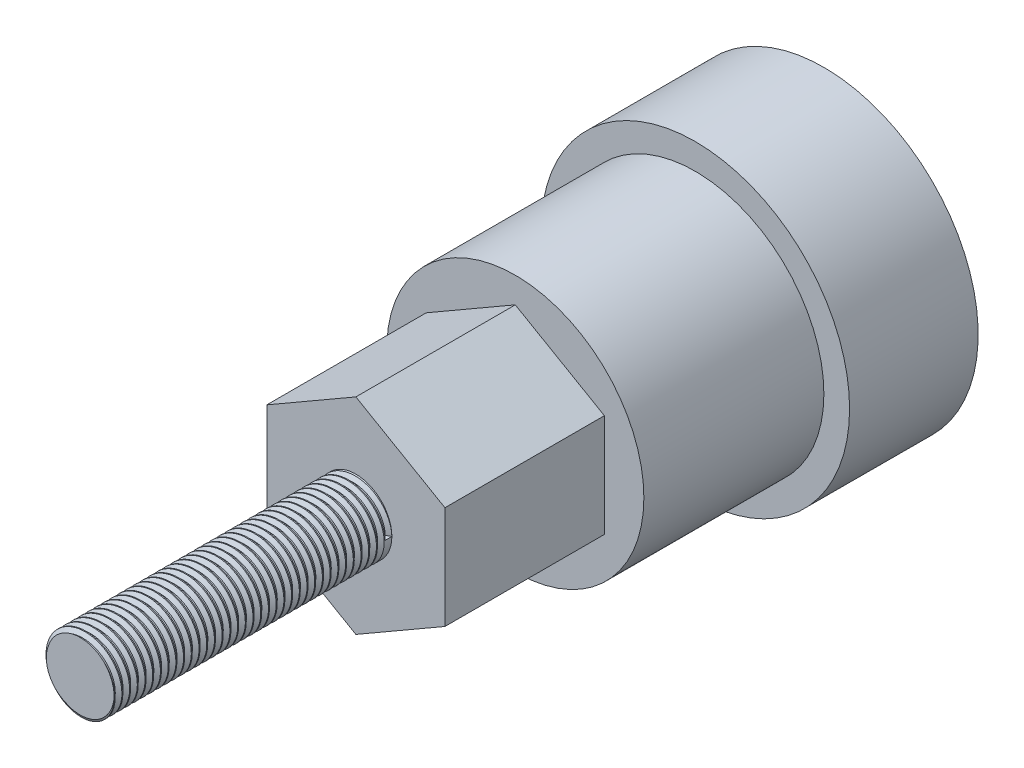
SolidWorks part; units mm, degrees
material "AISI 4340 Steel, annealed"
ref_plane "Front Plane" through (0, 0, 0) normal (0, 0, 1) x (1, 0, 0)
ref_plane "Top Plane" through (0, 0, 0) normal (0, 1, 0) x (1, 0, 0)
ref_plane "Right Plane" through (0, 0, 0) normal (1, 0, 0) x (0, 0, -1)
sketch "Sketch1" plane through (0, 0, 0) normal (0, 0, 1) x (1, 0, 0)
  circle A0 centre (0, 0) radius 30
  dimension "D1" = 60
extrude "Boss-Extrude1" add sketch "Sketch1" along normal blind 40
sketch "Sketch13" plane through (0, 0, 40) normal (0, 0, 1) x (1, 0, 0)
  circle A0 centre (0, 0) radius 25
  dimension "D1" = 50
extrude "Boss-Extrude7" add sketch "Sketch13" along normal blind 35
sketch "Sketch14" plane through (0, 0, 75) normal (0, 0, 1) x (1, 0, 0)
  line L5 (-19, 19) -> (19, -19) construction
  line L6 (-19, -19) -> (19, 19) construction
  line L7 (0, 20) -> (-17.3205, 10)
  line L8 (-17.3205, 10) -> (-17.3205, -10)
  line L9 (-17.3205, -10) -> (0, -20)
  line L10 (0, -20) -> (17.3205, -10)
  line L11 (17.3205, -10) -> (17.3205, 10)
  line L12 (17.3205, 10) -> (0, 20)
  circle A4 centre (0, 0) radius 17.3205 construction
  point P0 (0, 0)
  dimension "D1" = 38
extrude "Boss-Extrude8" add sketch "Sketch14" along normal blind 31
sketch "Sketch15" plane through (0, 0, 106) normal (0, 0, 1) x (1, 0, 0)
  circle A0 centre (0, 0) radius 7
  dimension "D1" = 14
extrude "Boss-Extrude9" add sketch "Sketch15" along normal blind 54
sketch "Sketch16" plane through (0, 0, 0) normal (0, 0, -1) x (-1, 0, 0)
  circle A0 centre (0, 0) radius 37.2164
extrude "Cut-Extrude2" cut sketch "Sketch16" against normal blind 15
hole_wizard "Ø2.5mm Dowel Hole2" [suppressed] positions "3DSketch3" profile "Sketch23" hole size "Ø2.5" standard "ANSI Metric"
sketch3d "3DSketch3"
  point P0 (-7, 0.0097, 120.8134)
sketch "Sketch23" plane through (-7, 0.0097, 120.8134) normal (0, 0, 1) x (-0.0014, -1, 0)
  line L0 (0, 0) -> (0, 37.0416)
  line L1 (0, 37.0416) -> (1.25, 37.0416)
  line L2 (1.25, 37.0416) -> (1.25, 0.025)
  line L3 (1.25, 0.025) -> (1.275, 0)
  line L5 (1.275, 0) -> (0, 0)
  line L6 (-1.25, 0.025) -> (-1.275, 0) construction
  line L11 (0, -6.35) -> (0, 107.95) construction
  dimension "Thru Hole Dia." = 2.5
  dimension "Thru Hole Depth" = 37.0416
  dimension "Near C'Sink Dia." = 2.55
  dimension "Near C'Sink Angle" = 90
thread "Thread1" pitch 1.5 method cut profile "Thread Profile1" start angle 0, offset 0, length 0, pitch 1.5, diameter 14
ref_plane "Plane1" through (7, 0, 106) normal (0, -1, 0) x (1, 0, 0)
sketch "Thread Profile1" plane through (7, 0, 106) normal (0, -1, 0) x (1, 0, 0)
  line L0 (0, 0) -> (0, 1.5) construction
  line L11 (0, 0) -> (0, 1.3125)
  line L12 (0, 1.3125) -> (-0.8119, 0.8437)
  line L13 (-0.8119, 0.8437) -> (-0.8119, 0.4687)
  line L15 (-0.8119, 0.4687) -> (0, 0)
  line L17 (-0.8119, 0.6562) -> (0, 0.6562) construction
  point P2 (0, 0)
  dimension "Pitch" = 1.5
  dimension "Profile_Angle" = 60
  dimension "Profile_Land" = 0.375
  dimension "Profile_Height" = 0.8119
sketch "Sketch24" plane through (0, 0, 15) normal (0, 0, -1) x (-1, 0, 0)
  point P0 (0, 0)
ref_plane "Plane2" through (0, 0, 40) normal (0, 0, 1) x (1, 0, 0)
